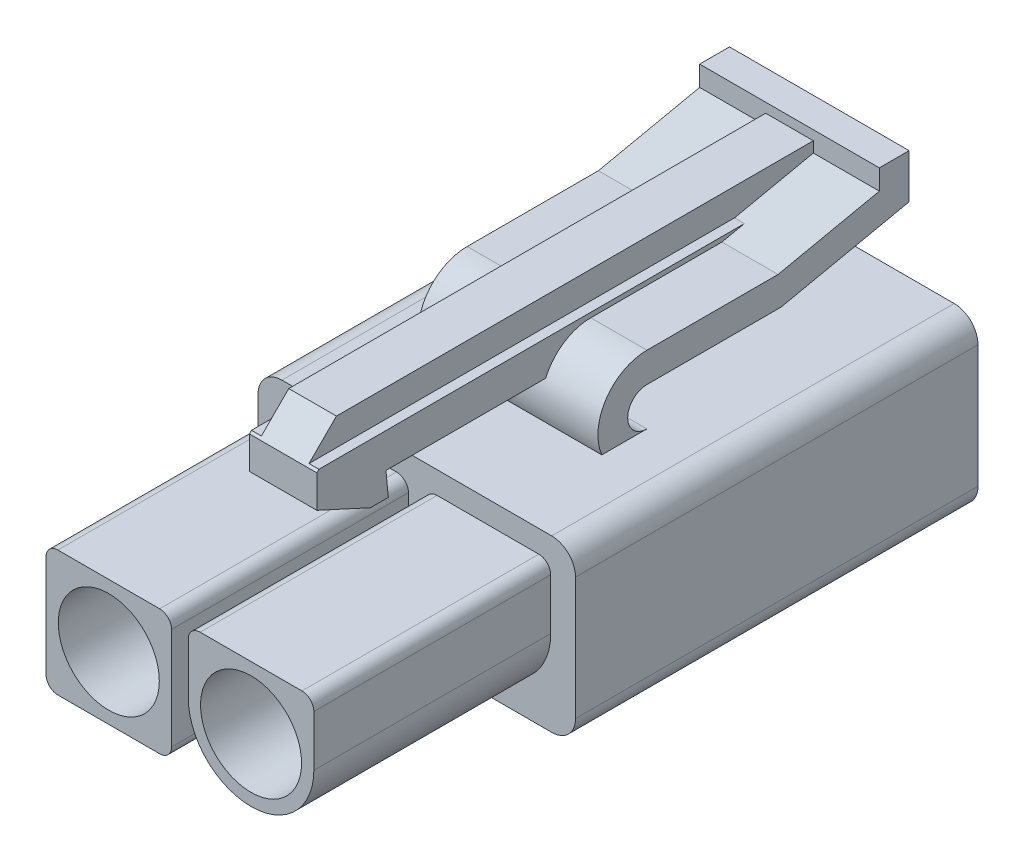
SolidWorks part; units mm, degrees
ref_plane "Front Plane" through (0, 0, 0) normal (0, 0, 1) x (1, 0, 0)
ref_plane "Top Plane" through (0, 0, 0) normal (0, 1, 0) x (1, 0, 0)
ref_plane "Right Plane" through (0, 0, 0) normal (1, 0, 0) x (0, 0, -1)
sketch "Sketch1" plane through (0, 0, 0) normal (0, 0, 1) x (1, 0, 0)
  line L1 (-6.66, -3.57) -> (6.66, -3.57)
  line L2 (-6.66, -3.57) -> (-6.66, 3.57)
  line L3 (-6.66, 3.57) -> (6.66, 3.57)
  line L4 (6.66, -3.57) -> (6.66, 3.57)
  line L5 (-6.66, -3.57) -> (6.66, 3.57) construction
  line L6 (-6.66, 3.57) -> (6.66, -3.57) construction
  point P0 (0, 0)
  dimension "D1" = 7.14
  dimension "D2" = 13.32
extrude "Boss-Extrude1" add sketch "Sketch1" against normal blind 16.89
sketch "Sketch2" plane through (0, 0, 0) normal (0, 0, 1) x (1, 0, 0)
  line L0 (0.35, 2.635) -> (0.35, 0)
  line L1 (-5.62, -2.635) -> (-0.35, -2.635)
  line L2 (-5.62, -2.635) -> (-5.62, 2.635)
  line L3 (-5.62, 2.635) -> (-0.35, 2.635)
  line L4 (-0.35, -2.635) -> (-0.35, 2.635)
  line L5 (-5.62, -2.635) -> (-0.35, 2.635) construction
  line L6 (-5.62, 2.635) -> (-0.35, -2.635) construction
  line L7 (5.62, 0) -> (5.62, 2.635)
  line L8 (5.62, 2.635) -> (0.35, 2.635)
  line L9 (-2.985, 0) -> (2.985, 0) construction
  arc A0 (0.35, 0) -> (5.62, 0) centre (2.985, 0) ccw
  point P0 (-2.985, 0)
  dimension "D1" = 5.27
  dimension "D2" = 11.24
extrude "Boss-Extrude2" add sketch "Sketch2" along normal offset from surface (9.94 mm away) 26.83 up to face at (0, 0, -16.89)
sketch "Sketch3" plane through (0, 0, 0) normal (0, 0, 1) x (1, 0, 0)
  line L0 (2.985, 0) -> (-2.985, 0) construction
  circle A0 centre (2.985, 0) radius 2.12
  circle A1 centre (-2.985, 0) radius 2.12
  dimension "D1" = 4.24
extrude "Cut-Extrude1" cut sketch "Sketch3" against normal through all both and the other way through all
sketch "Sketch4" plane through (0, 0, 0) normal (1, 0, 0) x (0, 0, -1)
  line L0 (5.885, 5.18) -> (11.5212, 5.18)
  line L1 (11.5212, 5.18) -> (16.89, 6.32)
  line L2 (16.89, 6.32) -> (16.89, 8.18)
  line L3 (16.89, 8.18) -> (15.64, 8.18)
  line L4 (15.64, 8.18) -> (15.64, 7.3324)
  line L5 (15.64, 7.3324) -> (11.39, 6.43)
  line L6 (11.39, 6.43) -> (5.885, 6.43)
  line L7 (16.89, 3.57) -> (0, 3.57) construction
  line L8 (3.9942, 3.57) -> (5.885, 3.57)
  line L9 (16.89, -3.57) -> (0, -3.57) construction
  line L10 (3.83, 4.375) -> (16.89, 4.375) construction
  line L11 (16.89, 4.375) -> (16.89, 6.32) construction
  line L12 (7.1795, 6.43) -> (7.1795, 5.18) construction
  line L13 (12.2207, 6.6064) -> (12.4803, 5.3837) construction
  line L14 (16.89, -3.57) -> (16.89, 3.57) construction
  arc A0 (5.885, 6.43) -> (3.9942, 3.57) centre (5.885, 4.375) ccw
  arc A1 (5.885, 5.18) -> (5.885, 3.57) centre (5.885, 4.375) ccw
  dimension "D1" = 1.25
  dimension "D2" = 10
  dimension "D3" = 13.06
  dimension "D4" = 11.75
  dimension "D5" = 2.75
  dimension "D6" = 5.5
extrude "Boss-Extrude3" add sketch "Sketch4" along normal mid plane 7.54
sketch "Sketch5" plane through (0, 0, 0) normal (1, 0, 0) x (0, 0, -1)
  line L0 (15.64, 7.78) -> (-4.3726, 7.78)
  line L1 (15.64, 8.18) -> (15.64, 7.3324) construction
  line L2 (-4.3726, 7.78) -> (-5.61, 6.5426)
  line L3 (-5.61, 6.5426) -> (-5.61, 5.18)
  line L4 (-5.61, 5.18) -> (-3.36, 4.15)
  line L6 (-2.71, 5.18) -> (5.5032, 5.18)
  line L7 (5.5032, 5.18) -> (15.64, 7.3324)
  line L8 (15.64, 7.3324) -> (15.64, 7.78)
  line L9 (15.64, 7.3324) -> (11.39, 6.43) construction
  line L11 (5.885, 5.18) -> (11.5212, 5.18) construction
  line L12 (16.89, 6.32) -> (16.89, 8.18) construction
  line L13 (-3.36, 4.15) -> (-2.61, 4.15)
  line L14 (-2.61, 4.15) -> (-2.71, 5.18)
  dimension "D1" = 2.6
  dimension "D2" = 22.5
  dimension "D3" = 135
  dimension "D4" = 1.75
  dimension "D5" = 3.63
  dimension "D6" = 3
  dimension "D7" = 2.9
  dimension "D8" = 0.75
extrude "Boss-Extrude4" add sketch "Sketch5" along normal mid plane 2.83
sketch "Sketch7" plane through (-1.415, 0, 0) normal (-1, 0, 0) x (0, 0, 1)
  line L0 (4.3726, 7.78) -> (5.61, 6.5426) construction
  line L1 (-15.64, 7.78) -> (4.3726, 7.78) construction
  line L2 (-15.64, 7.3324) -> (-15.64, 7.78) construction
  line L3 (-11.39, 6.43) -> (-15.64, 7.3324) construction
  line L4 (4.3726, 7.78) -> (5.5226, 6.63)
  line L5 (-15.64, 7.78) -> (4.3726, 7.78)
  line L6 (-15.64, 7.3324) -> (-15.64, 7.78)
  line L7 (-12.3319, 6.63) -> (-15.64, 7.3324)
  line L8 (5.5226, 6.63) -> (-12.3319, 6.63)
  dimension "D1" = 1.45
extrude "Cut-Extrude3" cut sketch "Sketch7" against normal blind 0.415
sketch "Sketch8" plane through (1.415, 0, 0) normal (1, 0, 0) x (0, 0, -1)
  line L5 (-4.3726, 7.78) -> (-5.5226, 6.63)
  line L6 (-5.5226, 6.63) -> (12.3319, 6.63)
  line L7 (12.3319, 6.63) -> (15.64, 7.3324)
  line L8 (15.64, 7.3324) -> (15.64, 7.78)
  line L9 (15.64, 7.78) -> (-4.3726, 7.78)
  line L10 (-4.3726, 7.78) -> (-5.5226, 6.63)
  line L11 (-5.5226, 6.63) -> (12.3319, 6.63)
  line L12 (12.3319, 6.63) -> (15.64, 7.3324)
  line L13 (15.64, 7.3324) -> (15.64, 7.78)
  line L14 (15.64, 7.78) -> (-4.3726, 7.78)
  dimension "D1" = 0
extrude "Cut-Extrude4" cut sketch "Sketch8" against normal blind 0.415
fillet "Fillet1" radius 1 4 edges at (6.66, 3.57, -8.445) (6.66, -3.57, -8.445) (-6.66, -3.57, -8.445) (-6.66, 3.57, -8.445)
fillet "Fillet2" radius 0.5 6 edges at (-5.62, -2.635, 4.97) (-0.35, -2.635, 4.97) (-5.62, 2.635, 4.97) (-0.35, 2.635, 4.97) (0.35, 2.635, 4.97) (5.62, 2.635, 4.97)
